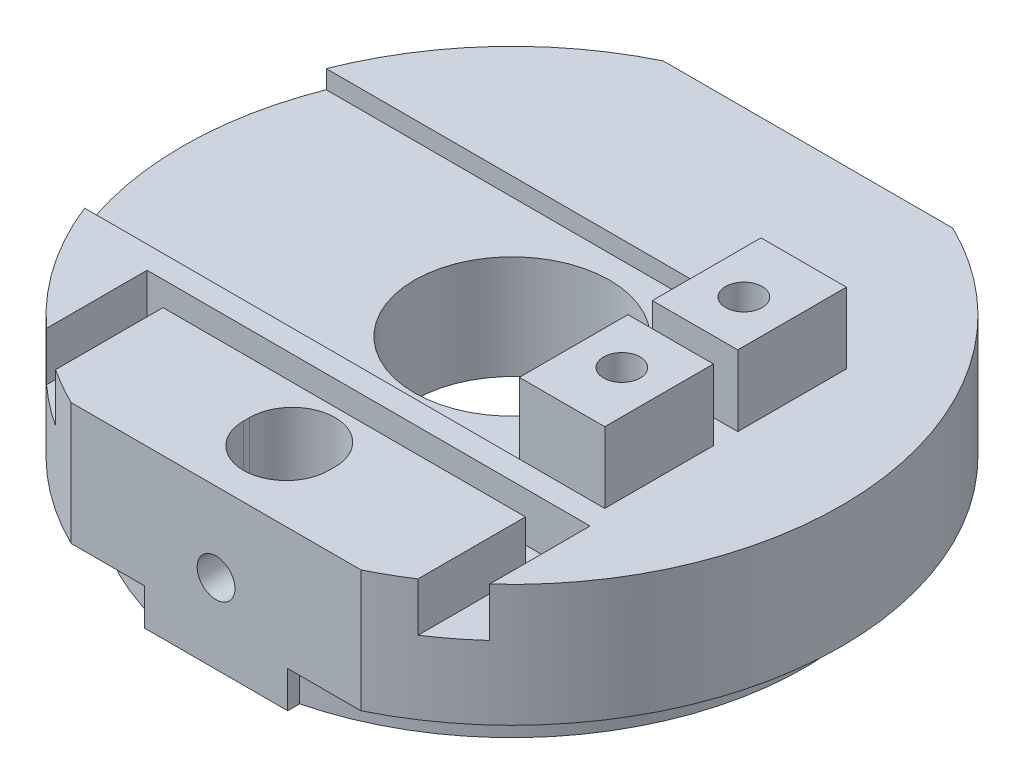
SolidWorks part; units mm, degrees
ref_plane "Front Plane" through (0, 0, 0) normal (0, 0, 1) x (1, 0, 0)
ref_plane "Top Plane" through (0, 0, 0) normal (0, 1, 0) x (1, 0, 0)
ref_plane "Right Plane" through (0, 0, 0) normal (1, 0, 0) x (0, 0, -1)
sketch "Sketch1" plane through (0, 0, 0) normal (0, 1, 0) x (1, 0, 0)
  line L0 (0, -18) -> (0, -18.5) construction
  line L5 (3.5, -18) -> (3.5, -18.5)
  line L6 (-3.5, -18) -> (-3.5, -18.5)
  line L7 (0, -14.5) -> (0, -8) construction
  line L8 (0, 27) -> (0, 24) construction
  line L9 (-17.5, -27) -> (17.5, -27)
  line L10 (-17.5, -27) -> (-17.5, -24.25)
  line L11 (-17.5, -24.25) -> (17.5, -24.25)
  line L12 (17.5, -27) -> (17.5, -24.25)
  line L13 (5.8745, -24.25) -> (-5.8745, -24.25)
  line L14 (5.8745, -24.25) -> (5.8745, -23.2699)
  line L15 (5.8745, -23.2699) -> (-5.8745, -23.2699)
  line L16 (-5.8745, -24.25) -> (-5.8745, -23.2699)
  line L18 (17.5, 27) -> (-17.5, 27)
  line L19 (17.5, 27) -> (17.5, 24.25)
  line L20 (17.5, 24.25) -> (-17.5, 24.25)
  line L21 (-17.5, 27) -> (-17.5, 24.25)
  circle A0 centre (0, 0) radius 8
  circle A1 centre (0, 0) radius 27
  circle A2 centre (0, 0) radius 24
  circle A3 centre (0, 0) radius 22
  arc A4 (3.5, -18) -> (-3.5, -18) centre (0, -18) ccw
  arc A5 (-3.5, -18.5) -> (3.5, -18.5) centre (0, -18.5) ccw
  circle A6 centre (0, 0) radius 20.75 construction
  circle A7 centre (0, 0) radius 14.5 construction
  point P12 (0, -18.25)
  point P17 (0, -14.5)
  point P18 (0, -22)
  point P23 (0, -27)
  point P24 (0, -23.2699)
  dimension "D1" = 16
  dimension "D2" = 54
  dimension "D3" = 48
  dimension "D4" = 44
  dimension "D5" = 3.5
  dimension "D8" = 41.5
  dimension "D9" = 29
  dimension "D6" = 7.5
  dimension "D7" = 6.5
  dimension "D10" = 35
  dimension "D11" = 24.25
  dimension "D12" = 11.749
extrude "Boss-Extrude1" add sketch "Sketch1" along normal blind 10 contours A2 L9 A1 | L9 A2 A3 | A3 A5 L6 A4 L5 A0 | L15 A2 | A2 L16 L11 region at (-15.1163, 0, -15.1163) region at (-26.2742, 0, 0) region at (-5.7566, 0, 23.76) region at (-14.3341, 0, -18.4025) region at (0, 0, 23.5623)
extrude "Boss-Extrude2" add sketch "Sketch1<3>" against normal blind 3 contours L9 A2 A3 | A2 L13 L14 | A2 L15 region at (-5.7566, 0, 23.76) region at (-14.3341, 0, -18.4025) region at (0, 0, 23.5623)
sketch "Sketch1<3>" plane through (0, 0, 0) normal (0, 1, 0) x (1, 0, 0) same geometry as "Sketch1"
sketch "Sketch2" plane through (0, 10, 0) normal (0, 1, 0) x (1, 0, 0)
  line L0 (0, -11.75) -> (0, -14.5) construction
  line L5 (-18.15, -24.25) -> (18.15, -24.25)
  line L6 (-18.15, -24.25) -> (-18.15, -11.75)
  line L7 (-18.15, -11.75) -> (18.15, -11.75)
  line L8 (18.15, -24.25) -> (18.15, -11.75)
  line L10 (-14.85, -24.25) -> (-14.85, -13.75)
  line L11 (-14.85, -13.75) -> (14.85, -13.75)
  line L12 (14.85, -13.75) -> (14.85, -24.25)
  line L13 (-14.85, -13.75) -> (-18.15, -13.75) construction
  line L14 (14.85, -13.75) -> (18.15, -13.75) construction
  line L15 (14.85, -13.75) -> (14.85, -11.75) construction
  line L16 (-11.8717, -24.25) -> (11.8717, -24.25) construction
  line L17 (25.1195, -9.9) -> (-25.1195, -9.9) construction
  arc A0 (3.5, -18) -> (-3.5, -18) centre (0, -18) ccw construction
  arc A1 (11.8717, -24.25) -> (11.8717, 24.25) centre (0, 0) ccw construction
  arc A2 (-11.8717, 24.25) -> (-11.8717, -24.25) centre (0, 0) ccw construction
  point P3 (0, -13.75)
  point P10 (-16.5, -13.75)
  point P21 (16.5, -13.75)
  point P22 (14.85, -12.75)
  dimension "D1" = 3.3
  dimension "D2" = 2
  dimension "D3" = 33
  dimension "D4" = 11.5
  dimension "D5" = 9.9
extrude "Cut-Extrude1" cut sketch "Sketch2" against normal blind 4 contours L11 L12 L8 L7 L6 L10 region at (-17.7661, 10, 18)
sketch "Sketch3" plane through (0, 10, 0) normal (0, 1, 0) x (1, 0, 0)
  line L1 (-27, 9.9) -> (10.5, 9.9)
  line L2 (-27, 9.9) -> (-27, -9.9)
  line L3 (-27, -9.9) -> (10.5, -9.9)
  line L4 (10.5, 9.9) -> (10.5, -9.9)
  arc A0 (18.15, -19.9894) -> (11.8717, 24.25) centre (0, 0) ccw construction
  point P4 (10.5, 0)
  dimension "D1" = 19.8
  dimension "D2" = 10.5
extrude "Cut-Extrude2" cut sketch "Sketch3" against normal blind 1.5
sketch "Sketch4" plane through (0, 10, 0) normal (0, 1, 0) x (1, 0, 0)
  line L0 (14, 5) -> (14, -5) construction
  line L1 (10.5, 9.9) -> (17.5, 9.9)
  line L2 (10.5, 9.9) -> (10.5, 1)
  line L3 (10.5, 1) -> (17.5, 1)
  line L4 (17.5, 9.9) -> (17.5, 1)
  line L5 (10.5, -9.9) -> (17.5, -9.9)
  line L6 (10.5, -9.9) -> (10.5, -1)
  line L7 (10.5, -1) -> (17.5, -1)
  line L8 (17.5, -9.9) -> (17.5, -1)
  line L9 (10.5, -9.9) -> (10.5, 9.9) construction
  line L10 (10.5, -9.9) -> (10.5, 9.9) construction
  circle A0 centre (14, 5) radius 1.5
  circle A1 centre (14, -5) radius 1.5
  point P14 (14, 0)
  point P16 (14, -9.9)
  point P20 (10.5, 0)
  dimension "D2" = 10
  dimension "D3" = 3
  dimension "D1" = 2
  dimension "D4" = 3.5
extrude "Boss-Extrude3" add sketch "Sketch4" along normal blind 5.8
sketch "Sketch5" plane through (0, 0, 24.25) normal (0, 0, 1) x (1, 0, 0)
  line L0 (18.15, 6) -> (14.85, 6) construction
  circle A0 centre (0, 3.5) radius 1.55
  dimension "D1" = 3.1
  dimension "D2" = 2.5
extrude "Cut-Extrude3" cut sketch "Sketch5" against normal blind 6
